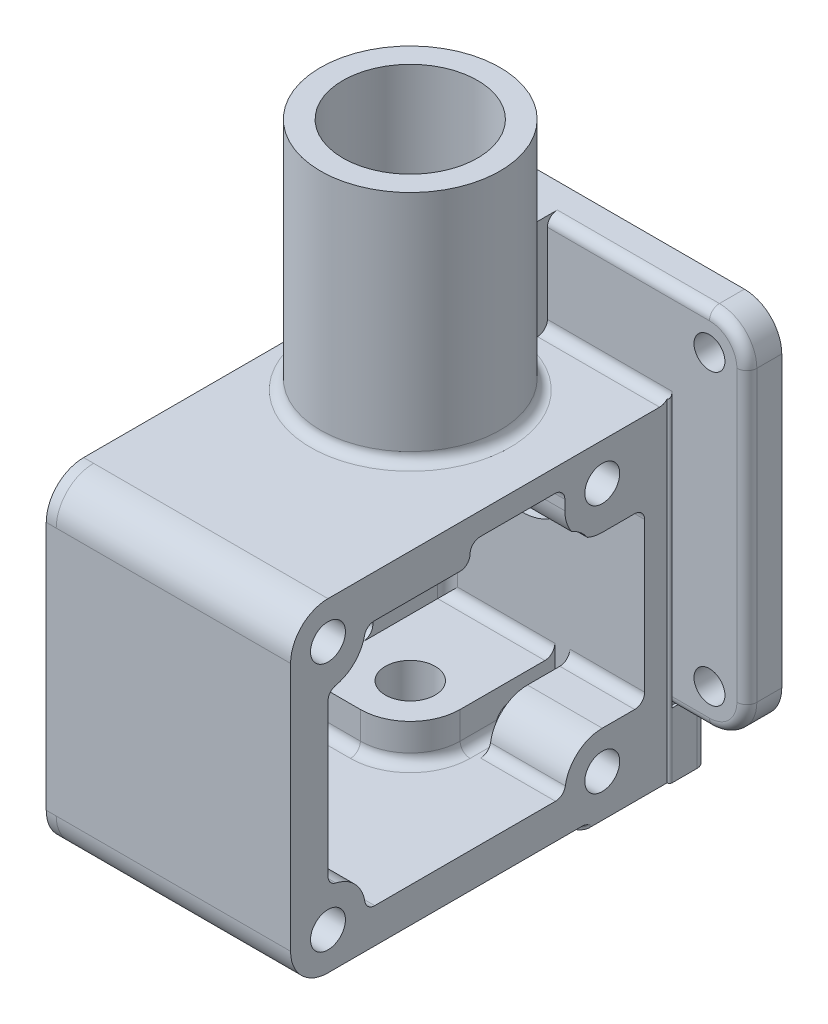
SolidWorks part; units mm, degrees
note: The reader was unsure of these and kept them because the rebuilt part matched: shared geometry of "Sketch9<4>", "Sketch10<2>".
ref_plane "Front Plane" through (0, 0, 0) normal (1, 0, 0) x (0, 1, 0)
ref_plane "Top Plane" through (0, 0, 0) normal (0, 0, 1) x (0, 1, 0)
ref_plane "Right Plane" through (0, 0, 0) normal (0, 1, 0) x (-1, 0, 0)
sketch "Sketch1" plane through (0, 0, 0) normal (0, 0, 1) x (0, 1, 0)
  line L1 (-36.5, 39) -> (36.5, 39)
  line L2 (-36.5, 39) -> (-36.5, -39)
  line L3 (-36.5, -39) -> (36.5, -39)
  line L4 (36.5, 39) -> (36.5, -39)
  line L5 (-36.5, 39) -> (36.5, -39) construction
  line L6 (-36.5, -39) -> (36.5, 39) construction
  point P0 (0, 0)
  dimension "D1" = 78
  dimension "D2" = 73
extrude "Boss-Extrude1" add sketch "Sketch1" along normal blind 7
fillet "Fillet27" radius 7.5 3 edges at (39, -36.5, 3.5) (-39, 36.5, 3.5) (39, 36.5, 3.5)
sketch "Sketch2" plane through (0, 0, 7) normal (0, 0, 1) x (1, 0, 0)
  circle A0 centre (-31.5, 29) radius 3.1
  circle A1 centre (31.5, 29) radius 3.1
  circle A2 centre (31.5, -29) radius 3.1
  circle A3 centre (-31.5, -29) radius 3.1
  dimension "D1" = 6.2
extrude "Cut-Extrude1" cut sketch "Sketch2" against normal through all both and the other way through all
sketch "Sketch4" plane through (0, 0, 0) normal (1, 0, 0) x (0, 1, 0)
  line L0 (-36.5, 0) -> (-49.5, 0)
  line L1 (-49.5, 0) -> (-49.5, 25)
  line L2 (-49.5, 25) -> (-48.5, 25)
  line L3 (-36.5, 0) -> (-36.5, 7) construction
  line L4 (-48.5, 25) -> (-48.5, 83)
  line L5 (-48.5, 83) -> (-41.5, 83)
  line L6 (-41.5, 83) -> (-41.5, 9)
  line L7 (-29, 7) -> (-36.5, 7) construction
  line L8 (-41.5, 9) -> (16.5, 9)
  line L9 (16.5, 9) -> (16.5, 7)
  line L10 (-29, 7) -> (29, 7) construction
  line L11 (16.5, 7) -> (-36.5, 7)
  line L12 (-36.5, 7) -> (-36.5, 0)
  dimension "D1" = 25
  dimension "D2" = 1
  dimension "D3" = 13
  dimension "D4" = 83
  dimension "D5" = 2
  dimension "7" = 7
  dimension "D6" = 58
extrude "Boss-Extrude2" add sketch "Sketch4" along normal mid plane 47
sketch "Sketch5" plane through (0, -49.5, 0) normal (0, -1, 0) x (1, 0, 0)
  line L0 (-25.5, 12) -> (-23.5, 12)
  line L1 (-23.5, 12) -> (-23.5, 7)
  line L2 (-23.5, 25) -> (-23.5, 0) construction
  line L3 (-23.5, 7) -> (-25.5, 7)
  line L4 (-39, 7) -> (-23.5, 7) construction
  line L5 (-25.5, 7) -> (-25.5, 12)
  line L6 (23.5, 25) -> (23.5, 0) construction
  line L7 (23.5, 7) -> (31.5, 7) construction
  line L8 (23.5, 7.5) -> (23.5, 7)
  line L9 (23.5, 7) -> (24, 7)
  arc A0 (23.5, 7.5) -> (24, 7) centre (23.5, 7) cw
  dimension "D3" = 0.5
  dimension "D1" = 12
  dimension "D2" = 2
extrude "Boss-Extrude3" add sketch "Sketch5" against normal up to surface (66 mm away) up to face at (0, 16.5, 8)
fillet "Fillet2" radius 2 1 edges at (-25.5, -10, 7)
sketch "Sketch6" plane through (23.5, 0, 0) normal (1, 0, 0) x (0, 1, 0)
  line L0 (-48.5, 83) -> (-41, 83) construction
  line L1 (-41, 83) -> (-41, 75.5) construction
  line L2 (-41, 75.5) -> (-41, 20.5) construction
  line L3 (-48.5, 83) -> (-48.5, 25) construction
  line L5 (16.5, 12) -> (-41.5, 12) construction
  line L6 (-33.5, 12) -> (-33.5, 28)
  line L8 (-41.5, 9) -> (16.5, 9)
  line L9 (16.5, 9) -> (16.5, 12)
  line L10 (16.5, 12) -> (-33.5, 12)
  line L11 (-48.5, 9) -> (-41.5, 9)
  line L13 (-33.5, 28) -> (-48.5, 28)
  line L15 (-48.5, 28) -> (-48.5, 9)
  dimension "D4" = 15
  dimension "D1" = 7.5
  dimension "D2" = 55
  dimension "D3" = 7.5
  dimension "D5" = 19
extrude "Boss-Extrude5" add sketch "Sketch6" against normal blind 15
fillet "Fillet7" radius 7.5 1 edges at (16, -33.5, 28)
sketch "Sketch7" plane through (0, 0, 12) normal (0, 0, 1) x (1, 0, 0)
  line L0 (-25.5, 16.5) -> (-23.5, 16.5)
  line L1 (-23.5, 16.5) -> (-23.5, -48.5)
  line L2 (-23.5, -48.5) -> (-25.5, -48.5)
  line L3 (-25.5, 16.5) -> (-25.5, -49.5) construction
  line L4 (-25.5, -48.5) -> (-25.5, 16.5)
extrude "Boss-Extrude7" add sketch "Sketch7" along normal up to surface (71 mm away) contours L1 L2 L4 L0 up to face at (0, -45, 83)
sketch "Sketch8" plane through (0, -36.5, 0) normal (0, -1, 0) x (1, 0, 0)
  line L0 (-25.5, 12) -> (-25.5, 7) construction
  line L1 (-27.5, 7) -> (-25.5, 7)
  line L2 (-25.5, 7) -> (-25.5, 9)
  arc A0 (-27.5, 7) -> (-25.5, 9) centre (-27.5, 9) ccw
  arc A1 (-27.5, 7) -> (-25.5, 9) centre (-27.5, 9) ccw construction
extrude "Boss-Extrude8" add sketch "Sketch8" along normal up to surface (13 mm away) up to face at (-2.4451, -49.5, 9.964)
sketch "Sketch9" plane through (-23.5, 0, 0) normal (1, 0, 0) x (0, 1, 0)
  line L0 (-49.5, 25) -> (-49.5, 7.5) construction
  line L1 (-11, 19.5) -> (-11, 12)
  line L2 (-29, 0) -> (29, 0) construction
  line L3 (16.5, 12) -> (-33.5, 12) construction
  line L4 (-18.5, 27) -> (-41.5, 27)
  line L5 (-41.5, 9) -> (-41.5, 83) construction
  line L6 (-41.5, 27) -> (-41.5, 12)
  line L7 (-41.5, 12) -> (-11, 12)
  line L8 (-41.5, 12) -> (-41.5, 9)
  line L11 (16.5, 9) -> (16.5, 12)
  line L12 (16.5, 12) -> (-41.5, 12)
  line L14 (16.5, 9) -> (-41.5, 9)
  arc A0 (-11, 19.5) -> (-18.5, 27) centre (-18.5, 19.5) ccw
  line M5 (-41.5, 83) -> (-41.5, 9)
  dimension "D3" = 15
  dimension "D1" = 31
  dimension "D2" = 19.5
extrude "Boss-Extrude9" add sketch "Sketch9" along normal blind 7.5 contours L1 A0 L4 L7 M5
extrude "Boss-Extrude10" add sketch "Sketch9<4>" along normal up to surface (32 mm away) contours L12 L11 L14 L8 up to face at (8.5, -22.3495, 17.1505)
sketch "Sketch9<4>" plane through (-23.5, 0, 0) normal (1, 0, 0) x (0, 1, 0) same geometry as "Sketch9"
sketch "Sketch10" plane through (0, -41.5, 0) normal (0, 1, 0) x (-1, 0, 0)
  line L0 (25.5, 9) -> (25.5, 83) construction
  line L1 (-31.5, 0) -> (31.5, 0) construction
  line L2 (-5.5, 31) -> (-5.5, 12)
  line L3 (23.5, 12) -> (-23.5, 12) construction
  line L4 (-5.5, 12) -> (23.5, 12)
  line L5 (23.5, 12) -> (23.5, 41)
  line L6 (23.5, 83) -> (23.5, 12) construction
  line L7 (23.5, 41) -> (4.5, 41)
  arc A0 (4.5, 41) -> (-5.5, 31) centre (4.5, 31) ccw
  circle A1 centre (4.5, 31) radius 5
  dimension "D3" = 20
  dimension "D4" = 10
  dimension "D1" = 21
  dimension "D2" = 31
extrude "Boss-Extrude11" add sketch "Sketch10" along normal blind 7.5
sketch "Sketch12" plane through (-23.5, 0, 0) normal (1, 0, 0) x (0, 1, 0)
  line L1 (16.5, 83) -> (-48.5, 83)
  line L2 (-48.5, 83) -> (-48.5, 75.5)
  line L3 (0.5, 20.5) -> (0.5, 7.5)
  line L4 (-48.5, 83) -> (-48.5, 25) construction
  line L5 (-33.5, 75.5) -> (0.5, 75.5)
  line L8 (0.5, 7.5) -> (16.5, 7.5)
  line L10 (8, 28) -> (12, 28)
  line L11 (12, 28) -> (12, 47)
  line L12 (12, 47) -> (8, 47)
  line L13 (8, 47) -> (8, 68)
  line L14 (16.5, 83) -> (16.5, 7.5)
  line L15 (16.5, 7.5) -> (0.5, 7.5)
  line L16 (16.5, 7) -> (16.5, 7.5) construction
  arc A0 (-48.5, 75.5) -> (-33.5, 75.5) centre (-41, 75.5) ccw
  arc A1 (0.5, 75.5) -> (8, 68) centre (8, 75.5) ccw
  arc A2 (8, 28) -> (0.5, 20.5) centre (8, 20.5) ccw
  line M19 (-11, 12) -> (16.5, 12)
  line M20 (16.5, 12) -> (16.5, 83)
  line M21 (16.5, 83) -> (-41.5, 83)
  line M22 (-41.5, 83) -> (-41.5, 41)
  dimension "D2" = 7.5
  dimension "D5" = 15
  dimension "D3" = 7.5
  dimension "D4" = 7.5
  dimension "D6" = 55
  dimension "D7" = 4
  dimension "D8" = 19
fillet "Fillet8" radius 7.5 2 edges at (-24.5, 16.5, 83) (-1, -48.5, 83)
fillet "Fillet10" radius 2 1 edges at (-23.5, 2.75, 12)
extrude "Boss-Extrude13" add sketch "Sketch12" along normal up to surface (47 mm away) contours L10 A2 L3 A0 L5 A1 L13 L12 L11 M19 M20 M21 M22 | L2 A0 L1 M22 up to face at (23.5, -32.1749, 29.7199)
fillet "Fillet32" radius 2 28 edges at (-23.5, 10, 28) (-23.5, 2.6967, 25.8033) (-23.5, 0.5, 17.25) (-22.9142, 0.5, 12.5858) (-18.75, -11, 12) (-22.9142, -11, 12.5858) (-23.5, -11, 16.75) (-23.5, -13.1967, 24.8033) (5.5, -41.5, 21.5) (2.5711, -41.5, 38.0711) (23.5, -49, 25) (0, -41.5, 68.0167) (0, -33.5, 75.5) (0, 12, 28) (0, 0.5, 75.5) (0, 8, 68) (0, 8, 47) (0, 12, 47) (-16, -22.5, 12) (1, 0.5, 12) (-5.25, -34, 12) (16, -33.5, 12) (-23.5, -26.25, 27) (-23.5, -37.75, 41) (-23.5, -34, 34) (-19.75, -34, 27) (-14, -41.5, 41) (16, -41.5, 28)
fillet "Fillet17" radius 7.5 2 edges at (0, -48.5, 83) (0, 16.5, 83)
sketch "Sketch15" plane through (-25.5, 0, 0) normal (-1, 0, 0) x (0, -1, 0)
  line L0 (3.5, 48) -> (3.5, 30) construction
  line L1 (11.5, 48) -> (11.5, 30)
  line L2 (-4.5, 48) -> (-4.5, 30)
  line L3 (-29, 0) -> (36.5, 0) construction
  line L4 (48.5, 75.5) -> (48.5, 12) construction
  circle A0 centre (-9, 75.5) radius 3.5
  circle A1 centre (41, 75.5) radius 3.5
  circle A2 centre (41, 20.5) radius 3.5
  circle A3 centre (-9, 20.5) radius 3.5
  arc A4 (48.5, 75.5) -> (41, 83) centre (41, 75.5) ccw construction
  arc A5 (11.5, 48) -> (-4.5, 48) centre (3.5, 48) ccw
  arc A6 (-4.5, 30) -> (11.5, 30) centre (3.5, 30) ccw
  point P9 (3.5, 39)
  dimension "D1" = 7
  dimension "D3" = 8
  dimension "D2" = 55
  dimension "D4" = 18
  dimension "D5" = 30
  dimension "D6" = 45
extrude "Cut-Extrude4" cut sketch "Sketch15" against normal through all both and the other way through all
sketch "Sketch16" plane through (-16, 0, 0) normal (1, 0, 0) x (0, 1, 0)
  line L0 (-29, 0) -> (29, 0) construction
  line L1 (-49.5, 23) -> (-49.5, 7.5) construction
  circle A0 centre (-18.5, 19.5) radius 3
  dimension "D1" = 6
  dimension "D2" = 19.5
  dimension "D3" = 31
extrude "Cut-Extrude5" cut sketch "Sketch16" against normal through all both and the other way through all
extrude "Cut-Extrude6" cut sketch "Sketch10<2>" against normal through all both and the other way through all contours A1
sketch "Sketch10<2>" plane through (0, -41.5, 0) normal (0, 1, 0) x (-1, 0, 0) same geometry as "Sketch10"
sketch "Sketch18" plane through (0, 16.5, 0) normal (0, 1, 0) x (-1, 0, 0)
  circle A0 centre (4.5, 31) radius 18
  dimension "D1" = 36
extrude "Boss-Extrude14" add sketch "Sketch18" along normal blind 47
sketch "Sketch19" plane through (0, 63.5, 0) normal (0, 1, 0) x (-1, 0, 0)
  circle A0 centre (4.5, 31) radius 12
  dimension "D1" = 24
extrude "Cut-Extrude7" cut sketch "Sketch19" against normal blind 42 and the other way through all
sketch "Sketch20" plane through (0, 63.5, 0) normal (0, 1, 0) x (-1, 0, 0)
  circle A0 centre (4.5, 31) radius 13.5
  dimension "D1" = 27
extrude "Cut-Extrude8" cut sketch "Sketch20" against normal blind 37
fillet "Fillet18" radius 2 1 edges at (-4.5, 21.5, 43)
fillet "Fillet19" radius 2 1 edges at (-4.5, 16.5, 13)
sketch "Sketch22" plane through (0, 21.5, 0) normal (0, 1, 0) x (-1, 0, 0)
  circle A0 centre (4.5, 31) radius 5
  dimension "D1" = 10
extrude "Cut-Extrude9" cut sketch "Sketch22" against normal mid plane 37
sketch "Sketch23" plane through (0, 0, 0) normal (0, 0, -1) x (1, 0, 0)
  line L0 (23.5, 49.5) -> (-23.5, 49.5) construction
  line L1 (-23.5, 36.5) -> (-23.5, 49.5) construction
  circle A0 centre (-1, 2.5) radius 10
  dimension "D1" = 20
  dimension "D2" = 47
  dimension "D3" = 22.5
extrude "Cut-Extrude10" cut sketch "Sketch23" against normal mid plane 70
sketch "Sketch24" plane through (0, 0, 7) normal (0, 0, 1) x (1, 0, 0)
  line L0 (-4.5, 63.5) -> (-4.5, 16.432) construction
  line L1 (9, 63.5) -> (-18, 63.5) construction
  line L2 (-24.4449, 36.5) -> (16.9893, 36.5) construction
  line L3 (31.5, 36.5) -> (-31.5, 36.5) construction
  line L4 (-8, 36.5) -> (-8, 16.5)
  line L6 (-1, 36.5) -> (-1, 16.5)
  line L7 (-8, 36.5) -> (-1, 36.5)
  line L8 (-1, 16.5) -> (-8, 16.5)
  dimension "D1" = 20
  dimension "D2" = 7
extrude "Boss-Extrude15" add sketch "Sketch24" along normal up to surface (6.3436 mm away)
fillet "Fillet20" radius 2 1 edges at (-4.5, 36.5, 13)
fillet "Fillet21" radius 2 1 edges at (-23.5, -36.5, 3.5)
fillet "Fillet22" radius 2 5 edges at (27.75, -36.5, 7) (36.8033, -34.3033, 7) (15.25, 36.5, 7) (36.8033, 34.3033, 7) (39, 0, 7)
fillet "Fillet24" radius 2 1 edges at (-39, -3.75, 7)
fillet "Fillet25" radius 2 2 edges at (-19.75, 36.5, 7) (-34.5006, 35.8736, 7)
sketch "Sketch25" plane through (0, -49.5, 0) normal (0, -1, 0) x (1, 0, 0)
  line L0 (-25.5, 12) -> (-25.5, 0)
  line L1 (-25.5, 0) -> (24, 0)
  line L2 (23.5, 0) -> (31.5, 0) construction
  line L3 (24, 0) -> (24, 7)
  line L5 (23.5, 7.5) -> (23.5, 12)
  line L6 (23.5, 23) -> (23.5, 7.5) construction
  line L7 (23.5, 12) -> (-25.5, 12)
  line L8 (23.5, 7.5) -> (23.5, 7)
  line L9 (23.5, 7) -> (24, 7)
extrude "Boss-Extrude16" add sketch "Sketch25" against normal up to surface (13 mm away) up to face at (-32.319, -36.5, 4.4024)
fillet "Fillet34" radius 2 1 edges at (24, -43, 0)
hole_wizard "Tap Drill for M5 Tap1" positions "3DSketch1" profile "Sketch27" hole size "M5" standard "ISO"
sketch3d "3DSketch1"
  line L0 (-23.5, -49.5, 25) -> (-23.5, -49.5, 12) construction
  line L1 (22, -49.5, 0) -> (-25.5, -49.5, 0) construction
  point P0 (-19.5, -49.5, 12.5)
  point P2 (17.5, -49.5, 12.5)
  dimension "D1" = 4
  dimension "D2" = 12.5
  dimension "D3" = 37
sketch "Sketch27" plane through (-19.5, -49.5, 12.5) normal (1, 0, 0) x (0, 0, -1)
  line L0 (0, 0) -> (0, 14.2618)
  line L1 (0, 14.2618) -> (2.1, 13)
  line L2 (2.1, 13) -> (2.1, 0)
  line L5 (2.1, 0) -> (0, 0)
  line L10 (0, 14.2618) -> (-2.1, 13) construction
  line L11 (0, -6.35) -> (0, 107.95) construction
  dimension "Hole Dia." = 4.2
  dimension "Hole Depth" = 13
  dimension "Drill Angle" = 118
fillet "Fillet29" radius 2 1 edges at (-32.25, -36.5, 7)
fillet "Fillet30" radius 7.5 2 edges at (-38.4142, -35.9142, 6.4142) (-39, -36.5, 2.5)
fillet "Fillet31" radius 2 1 edges at (-17.75, 16.5, 7)
sketch "Sketch28" plane through (-23.5, 0, 0) normal (-1, 0, 0) x (0, -1, 0)
  line L1 (48.5, 25) -> (49.5, 25)
  line L2 (48.5, 25) -> (48.5, 12)
  line L3 (48.5, 12) -> (49.5, 12)
  line L4 (49.5, 25) -> (49.5, 12)
extrude "Boss-Extrude17" add sketch "Sketch28" along normal up to surface (2 mm away) up to face at (-25.5, -24.375, 45.2633)
fillet "Fillet33" radius 2 1 edges at (-25.5, -49, 25)
sketch "Sketch30" plane through (0, -49.5, 0) normal (0, -1, 0) x (1, 0, 0)
  line L0 (-27.5, 7) -> (-27.5, 0)
  line L1 (-31.5, 0) -> (-25.5, 0) construction
  line L2 (-27.5, 0) -> (-25.5, 0)
  line L3 (-25.5, 0) -> (-25.5, 7)
  line L4 (-25.5, 7) -> (-27.5, 7)
extrude "Boss-Extrude18" add sketch "Sketch30" against normal up to next
fillet "Fillet35" radius 2 1 edges at (-27.5, -43, 0)
fillet "Fillet36" radius 2 1 edges at (11.5, 16.5, 7)
fillet "Fillet37" radius 0.5 3 edges at (22.9142, -48.5, 24.4142) (-24.9142, -48.5, 24.4142) (-1, -48.5, 25)
